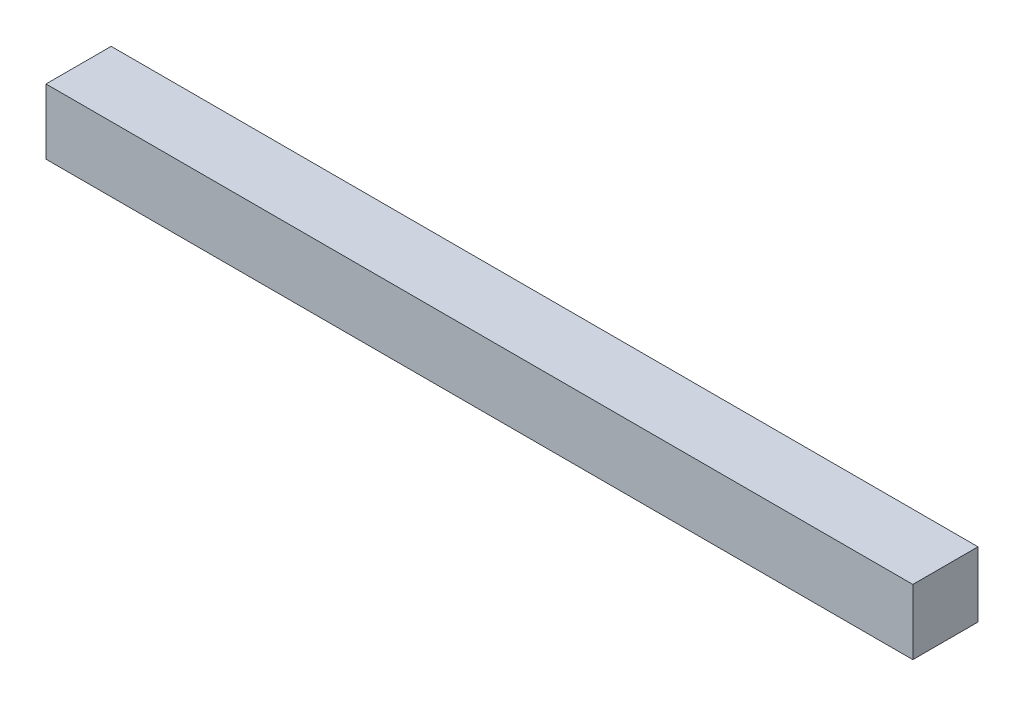
SolidWorks part; units mm, degrees
ref_plane "Plan de face" through (0, 0, 0) normal (0, 0, 1) x (1, 0, 0)
ref_plane "Plan de dessus" through (0, 0, 0) normal (0, 1, 0) x (1, 0, 0)
ref_plane "Plan de droite" through (0, 0, 0) normal (1, 0, 0) x (0, 0, -1)
sketch "Esquisse1" plane through (0, 0, 0) normal (0, 0, 1) x (1, 0, 0)
  line L1 (-70.6069, 40.1724) -> (62.3931, 40.1724)
  line L2 (-70.6069, 40.1724) -> (-70.6069, 30.1724)
  line L3 (-70.6069, 30.1724) -> (62.3931, 30.1724)
  line L4 (62.3931, 40.1724) -> (62.3931, 30.1724)
  dimension "D1" = 10
  dimension "D2" = 133
extrude "Boss.-Extru.1" add sketch "Esquisse1" along normal blind 10
equation "\"EpaisseurPlaque\"= 3"
equation "\"ProfondeurBoite\"=460"
equation "\"LongueurSyphon\"=170"
equation "\"LargeurSyphon\"=120"
equation "\"HauteurCoteDroit\"= 490"
equation "\"HauteurCoteGauche\"= 540"
equation "\"HauteurSolSyphon\"= 300"
equation "\"HauteurSyphon\"=\"HauteurCoteGauche\"-\"HauteurSolSyphon\""
equation "\"LargeurDroite\"=10"
equation "\"LargeurGauche\"=150"
equation "\"LargeurBoite\"= \"LargeurDroite\" + \"LargeurGauche\" + \"LargeurSyphon\""
equation "\"D2@Esquisse1\"=\"LargeurBoite\" - \"LargeurGauche\" + 3"
